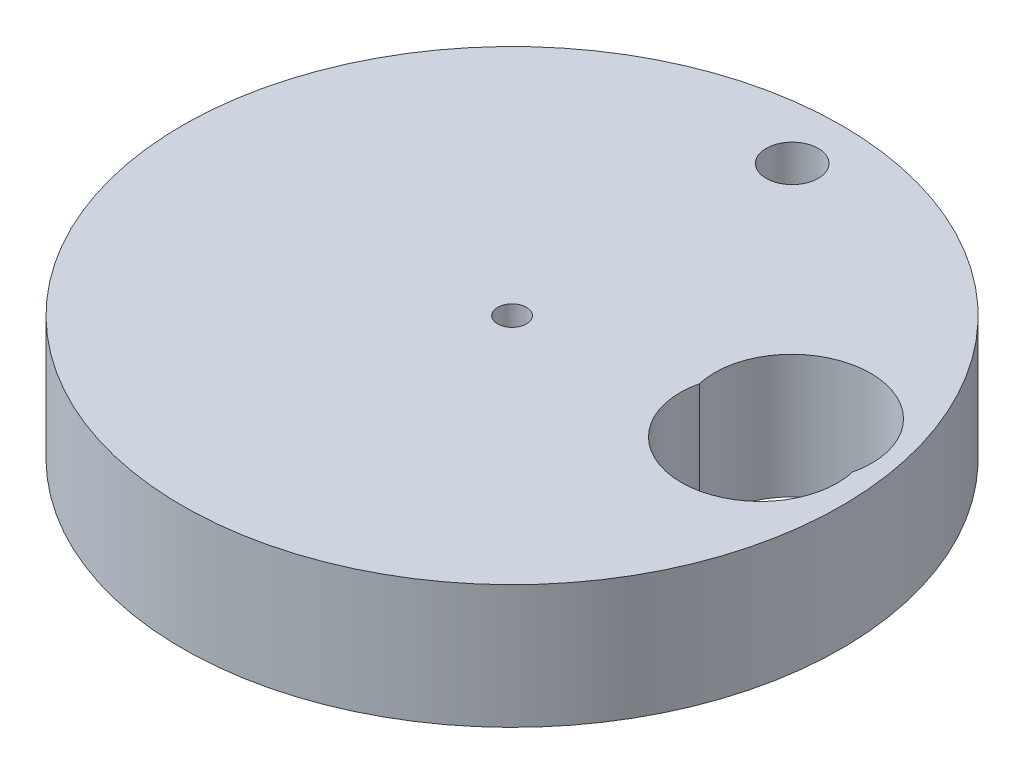
SolidWorks part; units mm, degrees
material "Polyurethane Foam Rigid"
ref_plane "Front Plane" through (0, 0, 0) normal (0, 0, 1) x (1, 0, 0)
ref_plane "Top Plane" through (0, 0, 0) normal (0, 1, 0) x (1, 0, 0)
ref_plane "Right Plane" through (0, 0, 0) normal (1, 0, 0) x (0, 0, -1)
sketch "Sketch1" plane through (0, 0, 0) normal (0, 1, 0) x (1, 0, 0)
  circle A0 centre (0, 0) radius 50.8
  circle A1 centre (1.27, 41.91) radius 4.0132 construction
  circle A2 centre (0, 0) radius 2.2225 construction
  circle A3 centre (1.27, 41.91) radius 4.0132
  circle A4 centre (0, 0) radius 2.2225
  ellipse E0 centre (35.325, 8.0287) end of major axis (47.425, 8.0287) minor radius 11.9162 construction
  ellipse E1 centre (35.325, 2.6804) end of major axis (47.425, 2.6804) minor radius 11.9162 (44.525, 10.4203) -> (44.525, -5.0596) ccw construction
  ellipse E2 centre (35.325, 8.0287) end of major axis (47.425, 8.0287) minor radius 11.9162
  ellipse E3 centre (35.325, 2.6804) end of major axis (47.425, 2.6804) minor radius 11.9162 (44.525, 10.4203) -> (44.525, -5.0596) ccw
  ellipse E4 centre (35.325, 2.6804) end of major axis (47.425, 2.6804) minor radius 11.9162 (44.525, -5.0596) -> (44.525, 10.4203) ccw construction
  ellipse E5 centre (35.325, 2.6804) end of major axis (47.425, 2.6804) minor radius 11.9162 (44.525, -5.0596) -> (44.525, 10.4203) ccw
  dimension "D1" = 101.6
extrude "Boss-Extrude1" add sketch "Sketch1" along normal blind 19.05 contours A0 E5 E3 E2 A4 A3 region at (-2.7605, 0, 0.7016)
